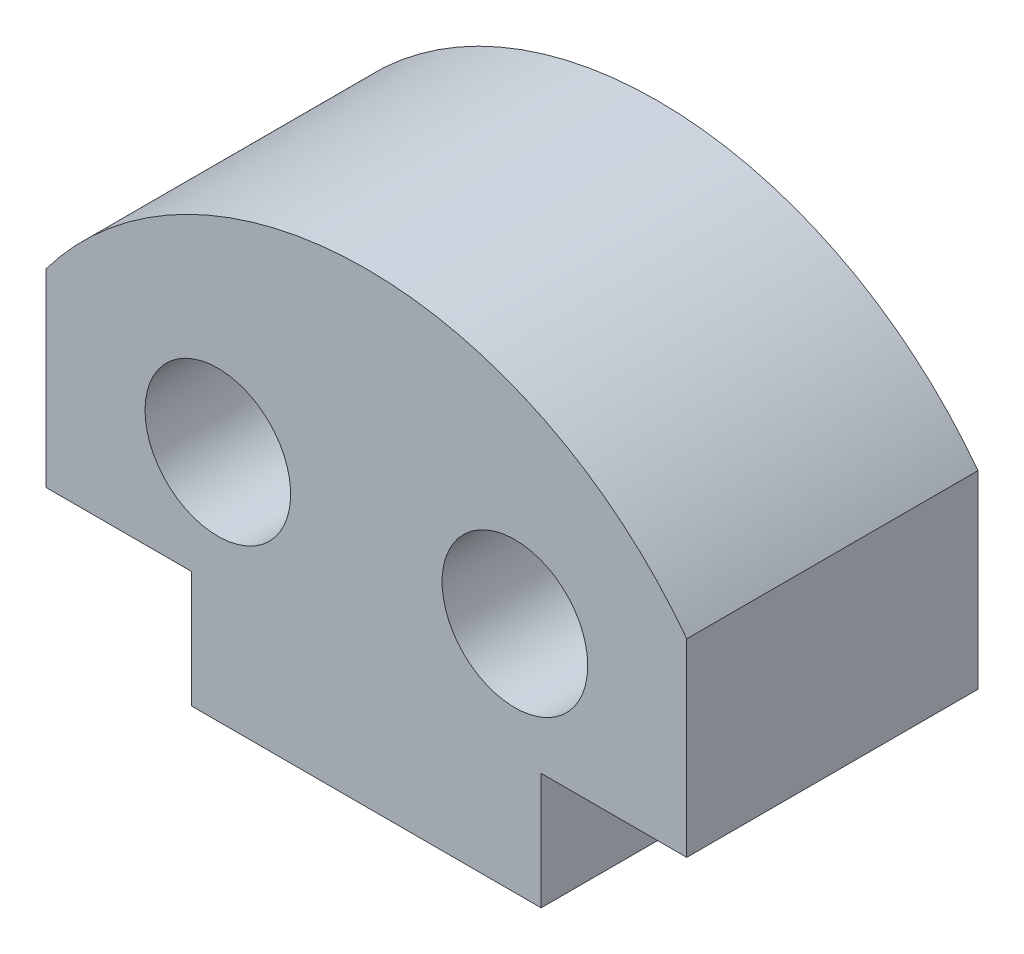
SolidWorks part; units mm, degrees
ref_plane "Front Plane" through (0, 0, 0) normal (0, 0, 1) x (1, 0, 0)
ref_plane "Top Plane" through (0, 0, 0) normal (0, 1, 0) x (1, 0, 0)
ref_plane "Right Plane" through (0, 0, 0) normal (1, 0, 0) x (0, 0, -1)
sketch "Model" plane through (0, 0, 0) normal (0, 0, 1) x (1, 0, 0)
  line L0 (0, 2) -> (-2.5, 2)
  line L1 (-2.5, 2) -> (-2.5, 5.25)
  line L2 (8.5, 2) -> (8.5, 5.25)
  line L3 (8.5, 2) -> (6, 2)
  line L4 (0, 2) -> (0, 0)
  line L5 (0, 0) -> (6, 0)
  line L6 (6, 0) -> (6, 2)
  line L7 (3, 0) -> (3, 4) construction
  arc A0 (8.5, 5.25) -> (-2.5, 5.25) centre (3, 1.125) ccw
  circle A1 centre (0.45, 4) radius 1.25
  circle A81 centre (5.55, 4) radius 1.25
  dimension "D1" = 2.5
  dimension "D2" = 6.875
  dimension "D3" = 2.55
extrude "Boss-Extrude1" add sketch "Model" along normal blind 5
